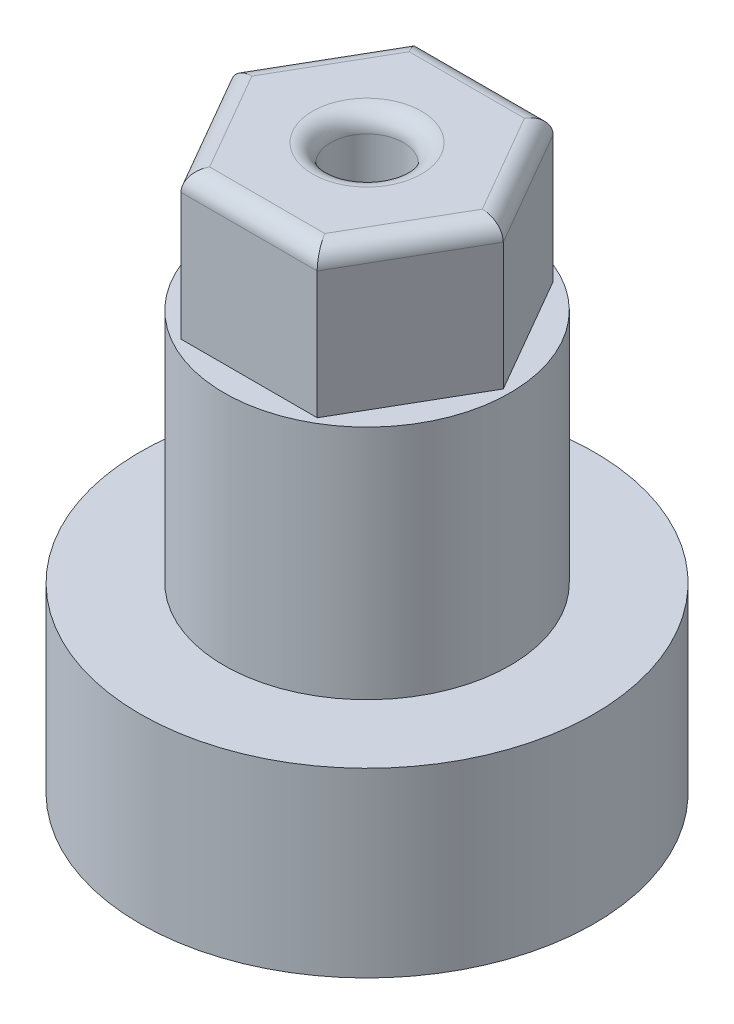
SolidWorks part; units mm, degrees
ref_plane "Alzado" through (0, 0, 0) normal (0, 0, 1) x (1, 0, 0)
ref_plane "Planta" through (0, 0, 0) normal (0, 1, 0) x (1, 0, 0)
ref_plane "Vista lateral" through (0, 0, 0) normal (1, 0, 0) x (0, 0, -1)
sketch "Croquis1" plane through (0, 0, 0) normal (0, 1, 0) x (1, 0, 0)
  line L0 (-12.5, 0) -> (12.5, 0) construction
  circle A0 centre (0, 0) radius 12.5
  circle A1 centre (7, 0) radius 0.75
  circle A2 centre (0, -7) radius 0.75
  circle A3 centre (-7, 0) radius 0.75
  circle A4 centre (0, 7) radius 0.75
  point P16 (0, 0)
  dimension "D1" = 25
  dimension "D2" = 1.5
  dimension "D3" = 7
  dimension "D4" = 4
extrude "Saliente-Extruir1" add sketch "Croquis1" along normal blind 10
sketch "Croquis2" plane through (0, 10, 0) normal (0, 1, 0) x (1, 0, 0)
  circle A0 centre (0, 0) radius 7.875
  dimension "D1" = 15.75
extrude "Saliente-Extruir2" add sketch "Croquis2" along normal blind 13
sketch "Croquis5" plane through (0, 10, 0) normal (0, 1, 0) x (1, 0, 0)
  circle A0 centre (0, 0) radius 12.5
sketch "Croquis3" plane through (0, 23, 0) normal (0, 1, 0) x (1, 0, 0)
  line L1 (7.5, 0) -> (3.75, 6.4952)
  line L2 (3.75, 6.4952) -> (-3.75, 6.4952)
  line L3 (-3.75, 6.4952) -> (-7.5, 0)
  line L4 (-7.5, 0) -> (-3.75, -6.4952)
  line L5 (-3.75, -6.4952) -> (3.75, -6.4952)
  line L6 (3.75, -6.4952) -> (7.5, 0)
  circle A0 centre (0, 0) radius 7.5 construction
extrude "Saliente-Extruir3" add sketch "Croquis3" along normal blind 8
sketch "Croquis4" plane through (0, 31, 0) normal (0, 1, 0) x (1, 0, 0)
  circle A0 centre (0, 0) radius 2
  dimension "D1" = 4
extrude "Cortar-Extruir1" cut sketch "Croquis4" against normal through all
fillet "Redondeo1" radius 1 7 edges at (0, 31, 6.4952) (-5.625, 31, 3.2476) (-5.625, 31, -3.2476) (0, 31, -6.4952) (5.625, 31, -3.2476) (5.625, 31, 3.2476) (0, 31, 2)
